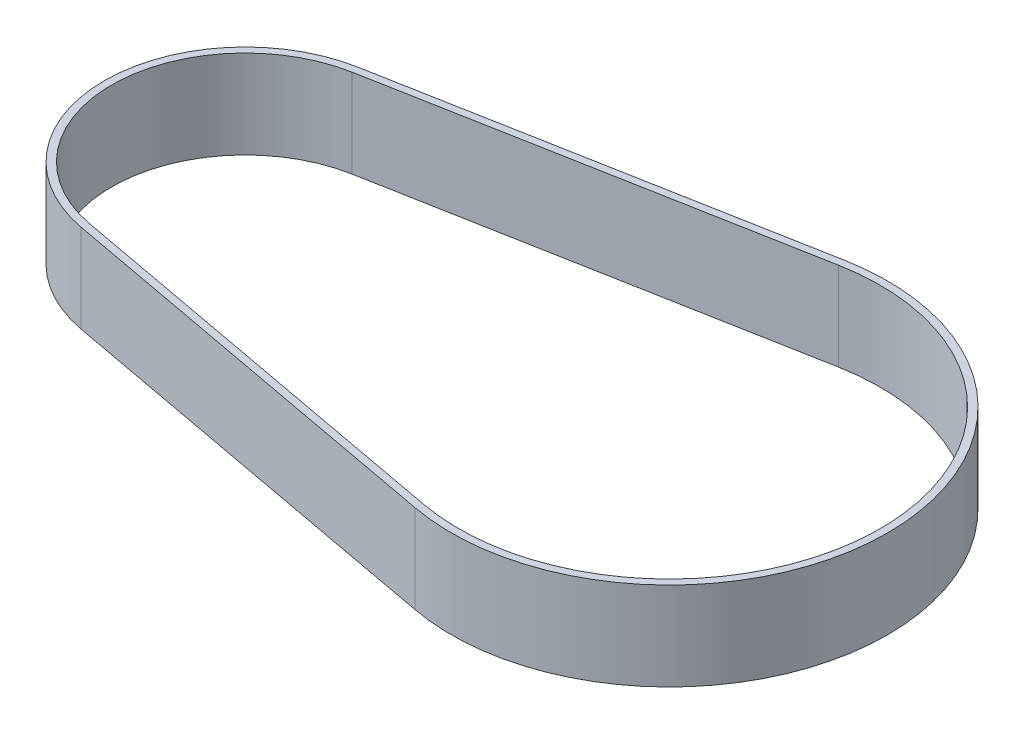
SolidWorks part; units mm, degrees
ref_plane "Plan de face" through (0, 0, 0) normal (0, 0, 1) x (1, 0, 0)
ref_plane "Plan de dessus" through (0, 0, 0) normal (0, 1, 0) x (1, 0, 0)
ref_plane "Plan de droite" through (0, 0, 0) normal (1, 0, 0) x (0, 0, -1)
sketch "Esquisse1" plane through (0, 0, 0) normal (0, 1, 0) x (1, 0, 0)
  line L0 (0, 0) -> (28.8314, 0) construction
  line L1 (-1.6532, 8.9181) -> (26.2204, 14.085)
  line L2 (-1.6532, -8.9181) -> (26.2204, -14.085)
  arc A2 (-1.6532, -8.9181) -> (-1.6532, 8.9181) centre (0, 0) cw
  arc A3 (26.2204, 14.085) -> (26.2204, -14.085) centre (28.8314, 0) cw
  dimension "D1" = 28.8314
  dimension "D2" = 14.325
  dimension "D3" = 9.07
extrude "Extru.-Mince1" add sketch "Esquisse1" along normal blind 6 thin thin type one direction wall 0.5
